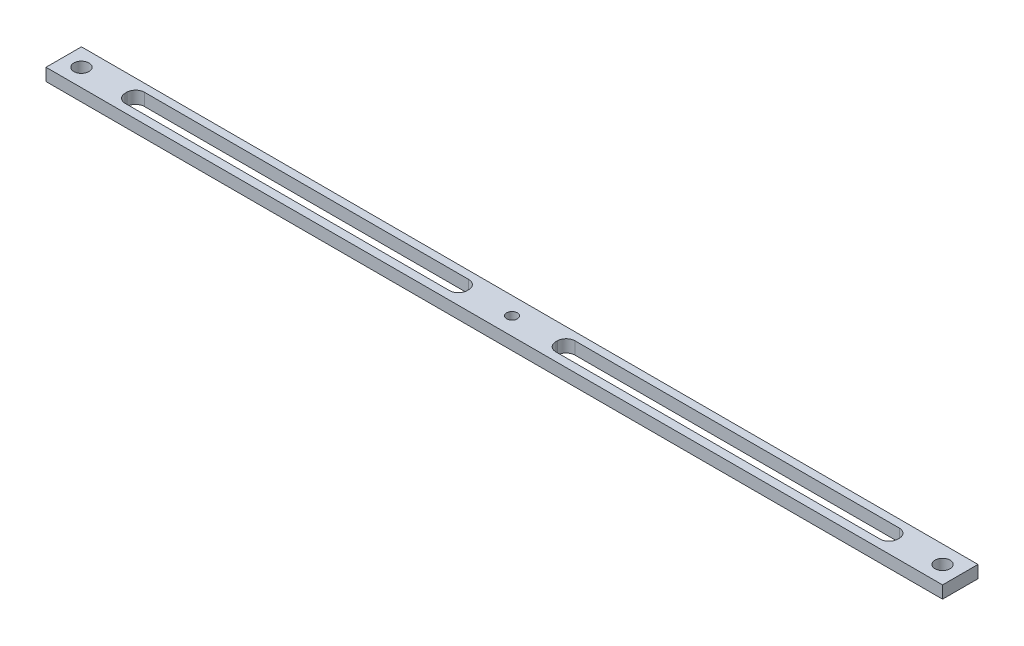
SolidWorks part; units mm, degrees
ref_plane "Płaszczyzna przednia" through (0, 0, 0) normal (0, 0, 1) x (1, 0, 0)
ref_plane "Płaszczyzna górna" through (0, 0, 0) normal (0, 1, 0) x (1, 0, 0)
ref_plane "Płaszczyzna prawa" through (0, 0, 0) normal (1, 0, 0) x (0, 0, -1)
sketch "Szkic1" plane through (0, 0, 0) normal (0, 1, 0) x (1, 0, 0)
  line L0 (253, 0) -> (253, 10)
  line L1 (0, 0) -> (506, 0)
  line L2 (0, 0) -> (0, 20)
  line L3 (0, 20) -> (506, 20)
  line L4 (506, 0) -> (506, 20)
  line L5 (0, 10) -> (10, 10)
  line L6 (506, 10) -> (496, 10)
  line L8 (40, 15.5746) -> (223, 15.5746)
  line L9 (35, 10.5746) -> (35, 9.6967)
  line L10 (40, 4.6967) -> (223, 4.6967)
  line L11 (228, 10.5746) -> (228, 9.6967)
  line L12 (283, 15.5746) -> (466, 15.5746)
  line L13 (278, 10.5746) -> (278, 9.7528)
  line L14 (283, 4.7528) -> (466, 4.7528)
  line L15 (471, 10.5746) -> (471, 9.7528)
  circle A0 centre (253, 10) radius 3
  circle A1 centre (10, 10) radius 4.25
  circle A2 centre (496, 10) radius 4.25
  arc A3 (466, 4.7528) -> (471, 9.7528) centre (466, 9.7528) ccw
  arc A4 (471, 10.5746) -> (466, 15.5746) centre (466, 10.5746) ccw
  arc A5 (283, 4.7528) -> (278, 9.7528) centre (283, 9.7528) cw
  arc A6 (283, 15.5746) -> (278, 10.5746) centre (283, 10.5746) ccw
  arc A7 (35, 9.6967) -> (40, 4.6967) centre (40, 9.6967) ccw
  arc A8 (223, 4.6967) -> (228, 9.6967) centre (223, 9.6967) ccw
  arc A9 (228, 10.5746) -> (223, 15.5746) centre (223, 10.5746) ccw
  arc A10 (40, 15.5746) -> (35, 10.5746) centre (40, 10.5746) ccw
  dimension "D1" = 5
  dimension "D2" = 20
  dimension "D6" = 8.5
  dimension "D7" = 6
  dimension "D8" = 8.5
  dimension "D11" = 35
  dimension "D3" = 506
  dimension "D4" = 183
  dimension "D5" = 183
  dimension "D9" = 10
  dimension "D10" = 10
  dimension "D12" = 35
extrude "Dodanie-wyciągnięcie1" add sketch "Szkic1" along normal blind 7 contours A0 L1 L4 L3 L2 region at (126.5, 0, -0.5064)
